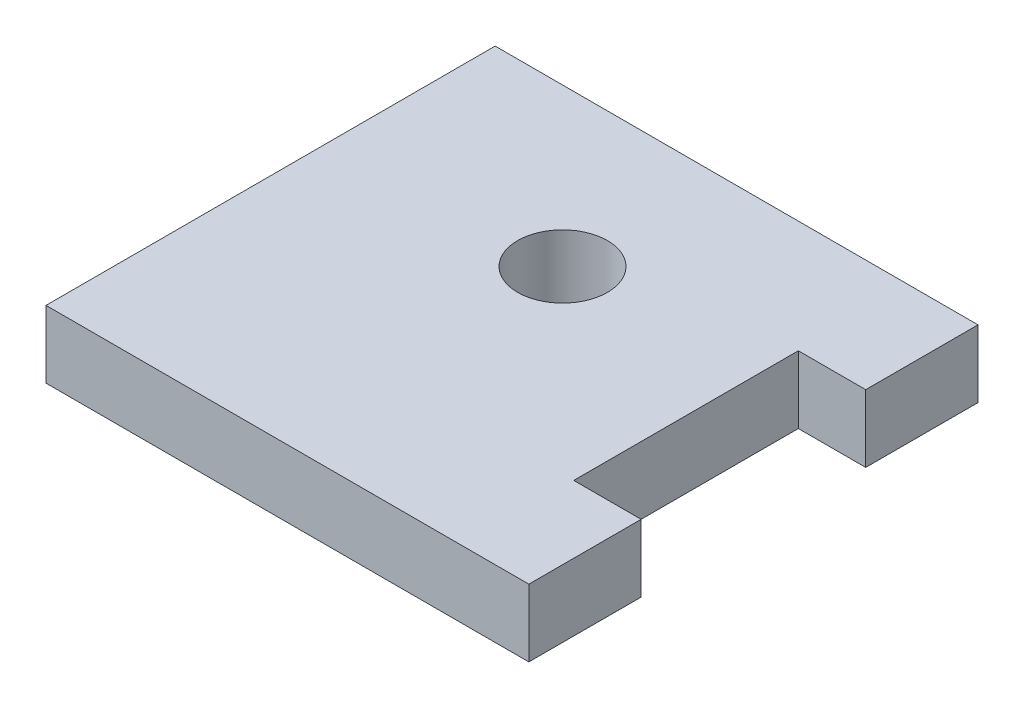
SolidWorks part; units mm, degrees
ref_plane "Front Plane" through (0, 0, 0) normal (0, 0, 1) x (1, 0, 0)
ref_plane "Top Plane" through (0, 0, 0) normal (0, 1, 0) x (1, 0, 0)
ref_plane "Right Plane" through (0, 0, 0) normal (1, 0, 0) x (0, 0, -1)
sketch "Sketch1" plane through (0, 0, 0) normal (0, 1, 0) x (1, 0, 0)
  line L9 (0, 0) -> (21.5, 0)
  line L17 (0, 0) -> (0, 20)
  line L18 (0, 20) -> (21.5, 20)
  line L19 (21.5, 0) -> (21.5, 5)
  line L20 (21.5, 15) -> (18.5, 15)
  line L22 (21.5, 5) -> (18.5, 5)
  line L23 (18.5, 15) -> (18.5, 5)
  line L24 (21.5, 15) -> (21.5, 20)
  circle A1 centre (10, 13) radius 2
  point P9 (0, 0)
  dimension "D6" = 7
  dimension "D7" = 4
  dimension "D1" = 20
  dimension "D2" = 21.5
  dimension "D3" = 3
  dimension "D4" = 5
  dimension "D5" = 10
  dimension "D8" = 10
extrude "Boss-Extrude1" add sketch "Sketch1" along normal blind 3
